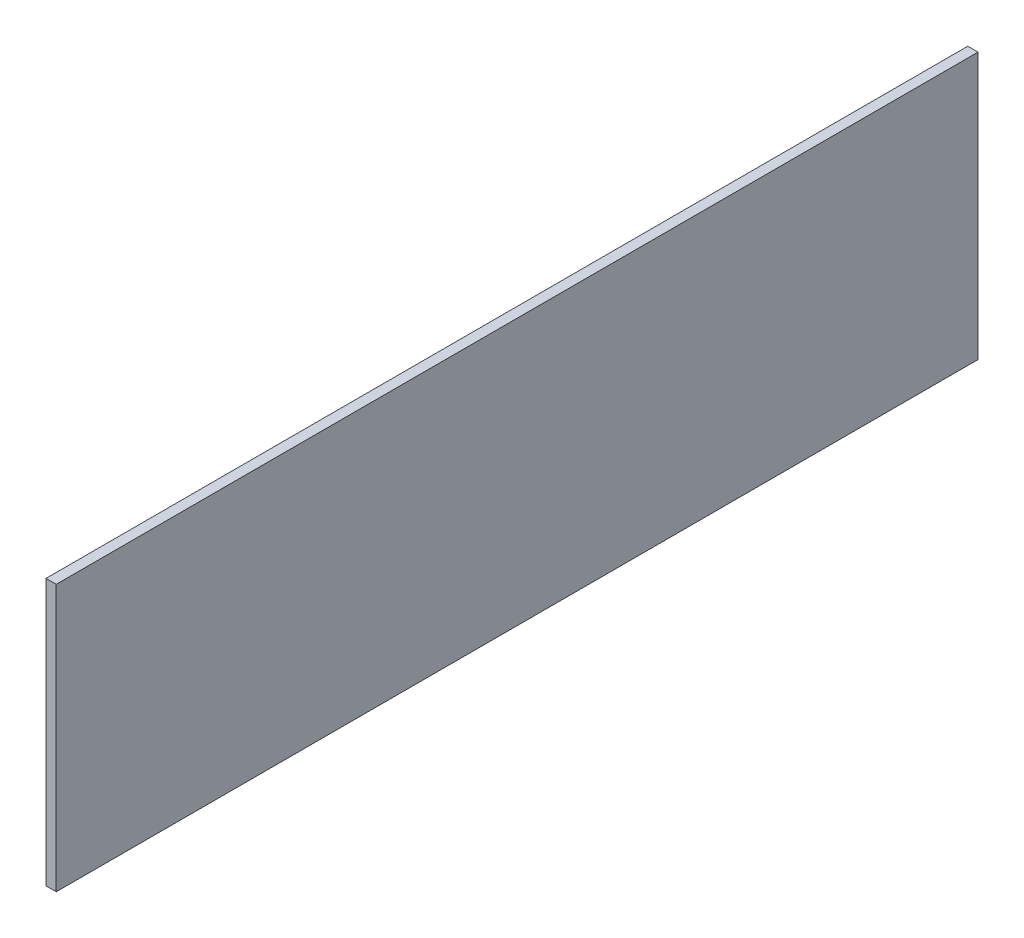
SolidWorks part; units mm, degrees
ref_plane "Front Plane" through (0, 0, 0) normal (1, 0, 0) x (0, 1, 0)
ref_plane "Top Plane" through (0, 0, 0) normal (0, 0, 1) x (0, 1, 0)
ref_plane "Right Plane" through (0, 0, 0) normal (0, 1, 0) x (-1, 0, 0)
sketch "Sketch1" plane through (0, 0, 0) normal (1, 0, 0) x (0, 1, 0)
  line L1 (0, 900) -> (520, 900)
  line L2 (0, 900) -> (0, -900)
  line L3 (0, -900) -> (520, -900)
  line L4 (520, 900) -> (520, -900)
  dimension "D1" = 1800
  dimension "D2" = 520
extrude "Boss-Extrude1" add sketch "Sketch1" along normal blind 10 and the other way blind 10
